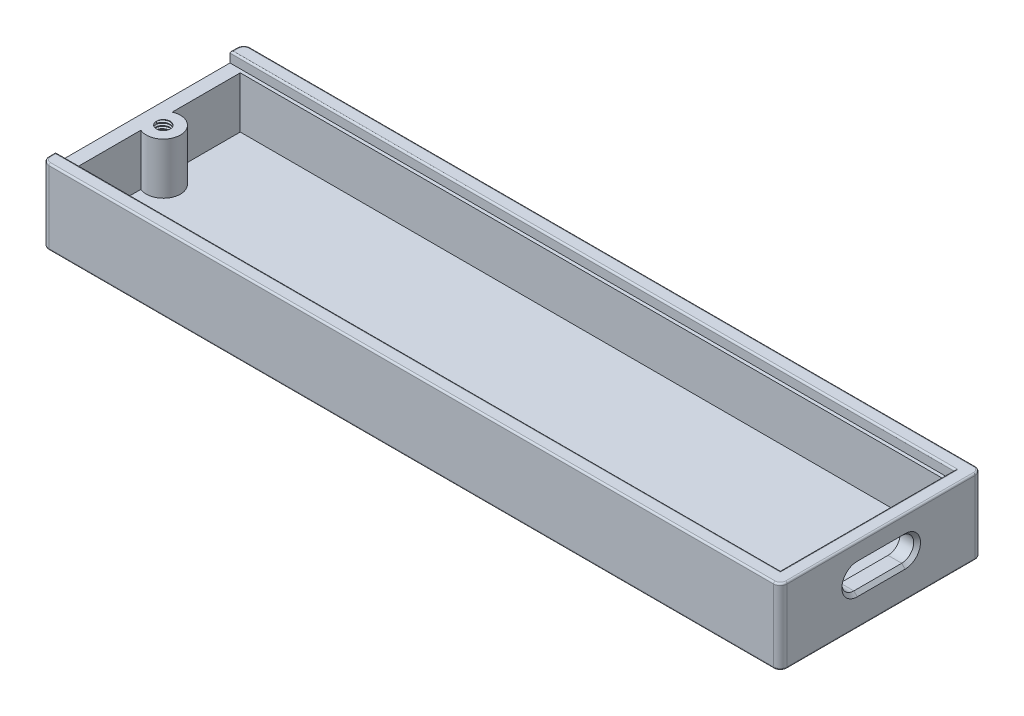
SolidWorks part; units mm, degrees
material "ABS"
ref_plane "Front Plane" through (0, 0, 0) normal (0, 0, 1) x (1, 0, 0)
ref_plane "Top Plane" through (0, 0, 0) normal (0, 1, 0) x (1, 0, 0)
ref_plane "Right Plane" through (0, 0, 0) normal (1, 0, 0) x (0, 0, -1)
sketch "Sketch1" plane through (0, 0, 0) normal (0, 1, 0) x (1, 0, 0)
  line L1 (0, 0) -> (108, 0)
  line L2 (0, 0) -> (0, -29.5)
  line L3 (0, -29.5) -> (108, -29.5)
  line L4 (108, 0) -> (108, -29.5)
  dimension "D1" = 108
  dimension "D2" = 29.5
extrude "Boss-Extrude1" add sketch "Sketch1" against normal blind 11
sketch "Sketch2" plane through (0, 0, 0) normal (0, 1, 0) x (1, 0, 0)
  line L0 (0, -29.5) -> (108, -29.5) construction
  line L1 (0, -2) -> (106, -2)
  line L2 (0, -2) -> (0, -27.5)
  line L3 (0, -27.5) -> (106, -27.5)
  line L4 (106, -2) -> (106, -27.5)
  line L6 (108, -29.5) -> (108, 0) construction
  line L8 (0, 0) -> (0, -29.5) construction
  line L10 (108, 0) -> (0, 0) construction
  dimension "D1" = 2
  dimension "D2" = 2
  dimension "D3" = 2
extrude "Cut-Extrude1" cut sketch "Sketch2" against normal blind 1.5
sketch "Sketch3" plane through (0, 0, 0) normal (0, 1, 0) x (1, 0, 0)
  line L0 (106, -2) -> (0, -2) construction
  line L1 (2, -2.5) -> (105.5, -2.5)
  line L2 (2, -2.5) -> (2, -27)
  line L3 (2, -27) -> (105.5, -27)
  line L4 (105.5, -2.5) -> (105.5, -27)
  line L5 (106, -27.5) -> (106, -2) construction
  line L6 (0, -27.5) -> (106, -27.5) construction
  line L7 (0, -2) -> (0, -27.5) construction
  dimension "D1" = 0.5
  dimension "D2" = 0.5
  dimension "D3" = 0.5
  dimension "D4" = 2
extrude "Cut-Extrude2" cut sketch "Sketch3" against normal blind 9
fillet "Fillet1" radius 0.25 12 edges at (0, 0, 1) (54, 0, 0) (108, 0, 14.75) (54, 0, 29.5) (0, 0, 28.5) (53, 0, 27.5) (106, 0, 14.75) (53, 0, 2) (54, -11, 29.5) (108, -11, 14.75) (54, -11, 0) (0, -11, 14.75)
fillet "Fillet2" radius 1 12 edges at (107.9268, -0.0732, 29.4268) (107.9268, -0.0732, 0.0732) (0.0732, -0.0732, 0.0732) (0.0732, -0.0732, 29.4268) (0, -5.5, 29.5) (0, -5.5, 0) (108, -5.5, 0) (108, -5.5, 29.5) (107.9268, -10.9268, 29.4268) (107.9268, -10.9268, 0.0732) (0.0732, -10.9268, 0.0732) (0.0732, -10.9268, 29.4268)
sketch "Sketch4" plane through (0, -9, 0) normal (0, 1, 0) x (1, 0, 0)
  line L0 (0, -2) -> (0, -27.5) construction
  circle A0 centre (3, -14.75) radius 2.5
  dimension "D1" = 5
  dimension "D2" = 3
extrude "Boss-Extrude2" add sketch "Sketch4" along normal up to surface (7.5 mm away) up to face at (53.75, -1.5, 14.75)
hole_wizard "Ø2.0 (2) Diameter Hole1" positions "3DSketch1" profile "Sketch5" hole size "Ø2.0" standard "ISO"
sketch3d "3DSketch1"
  line L0 (0, -1.5, 2) -> (0, -1.5, 27.5) construction
  line L2 (106, -1.5, 2) -> (0, -1.5, 2) construction
  point P0 (3, -1.5, 14.75)
  point P7 (3, -1.5, 14.6576)
  dimension "D1" = 3
  dimension "D2" = 12.75
sketch "Sketch5" plane through (3, -1.5, 14.75) normal (1, 0, 0) x (0, 0, 1)
  line L0 (0, 0) -> (0, 5.6009)
  line L1 (0, 5.6009) -> (1, 5)
  line L2 (1, 5) -> (1, 0)
  line L5 (1, 0) -> (0, 0)
  line L10 (0, 5.6009) -> (-1, 5) construction
  line L11 (0, -6.35) -> (0, 107.95) construction
  dimension "Hole Dia." = 2
  dimension "Hole Depth" = 5
  dimension "Drill Angle" = 118
thread "Thread1" pitch 0.4 method cut profile "Thread Profile1" start angle 0, offset 0, length 4, pitch 0.4, diameter 2
ref_plane "Plane4" through (2, -1.5, 14.75) normal (0, 0, 1) x (-1, 0, 0)
sketch "Thread Profile1" plane through (2, -1.5, 14.75) normal (0, 0, 1) x (-1, 0, 0)
  line L0 (0, 0) -> (0, 0.4) construction
  line L1 (0, 0) -> (0.2165, 0.125)
  line L2 (0.2165, 0.125) -> (0.2165, 0.175)
  line L3 (0.2165, 0.175) -> (0, 0.3)
  line L4 (0.2165, 0.15) -> (0, 0.15) construction
  line L11 (0, 0) -> (0, 0.3)
  point P2 (0, 0)
  dimension "Pitch" = 0.4
  dimension "Profile_Angle" = 60
  dimension "Profile_Land" = 0.05
  dimension "Profile_Height" = 0.2165
sketch "Sketch9" plane through (108, 0, 0) normal (1, 0, 0) x (0, 0, -1)
  line L0 (-18.25, -4.75) -> (-11.25, -4.75) construction
  line L1 (-18.25, -3) -> (-11.25, -3)
  line L2 (-18.25, -6.5) -> (-11.25, -6.5)
  line L3 (-28.5, -10.75) -> (-1, -10.75) construction
  line L5 (-29.5, -10.75) -> (-29.5, -0.25) construction
  arc A0 (-18.25, -3) -> (-18.25, -6.5) centre (-18.25, -4.75) ccw
  arc A1 (-11.25, -6.5) -> (-11.25, -3) centre (-11.25, -4.75) ccw
  point P2 (-14.75, -4.75)
  dimension "D1" = 7
  dimension "D2" = 6
  dimension "D3" = 3.5
  dimension "D4" = 14.75
extrude "Cut-Extrude3" cut sketch "Sketch9" against normal up to next
chamfer "Chamfer1" distance 0.5 angle 45 4 edges at (108, -4.75, 9.5) (108, -3, 14.75) (108, -4.75, 20) (108, -6.5, 14.75)
sketch "Sketch10" plane through (0, -11, 0) normal (0, -1, 0) x (1, 0, 0)
  line L0 (107, 29.25) -> (1, 29.25) construction
  line L1 (0.25, 28.5) -> (0.25, 1) construction
  line L2 (0.25, 14.75) -> (107.75, 14.75) construction
  line L4 (54, 29.25) -> (54, 0) construction
  circle A0 centre (3.25, 26.25) radius 0.75
  circle A1 centre (3.25, 3.25) radius 0.75
  circle A2 centre (104.75, 3.25) radius 0.75
  circle A3 centre (104.75, 26.25) radius 0.75
  dimension "D3" = 1.5
  dimension "D1" = 3
  dimension "D2" = 3
extrude "Boss-Extrude3" add sketch "Sketch10" along normal blind 0.5
fillet "Fillet3" radius 0.25 4 edges at (3.25, -11.5, 25.5) (104.75, -11.5, 27) (104.75, -11.5, 2.5) (3.25, -11.5, 4)
sketch "Sketch11" plane through (106, 0, 0) normal (-1, 0, 0) x (0, 0, 1)
  line L0 (27.5, -1.5) -> (27.5, -0.25) construction
  line L1 (2, -1.5) -> (27.5, -1.5)
  line L2 (2, -1.5) -> (2, -0.875)
  line L3 (2, -0.875) -> (27.5, -0.875)
  line L4 (27.5, -1.5) -> (27.5, -0.875)
extrude "Cut-Extrude4" cut sketch "Sketch11" against normal blind 0.5
